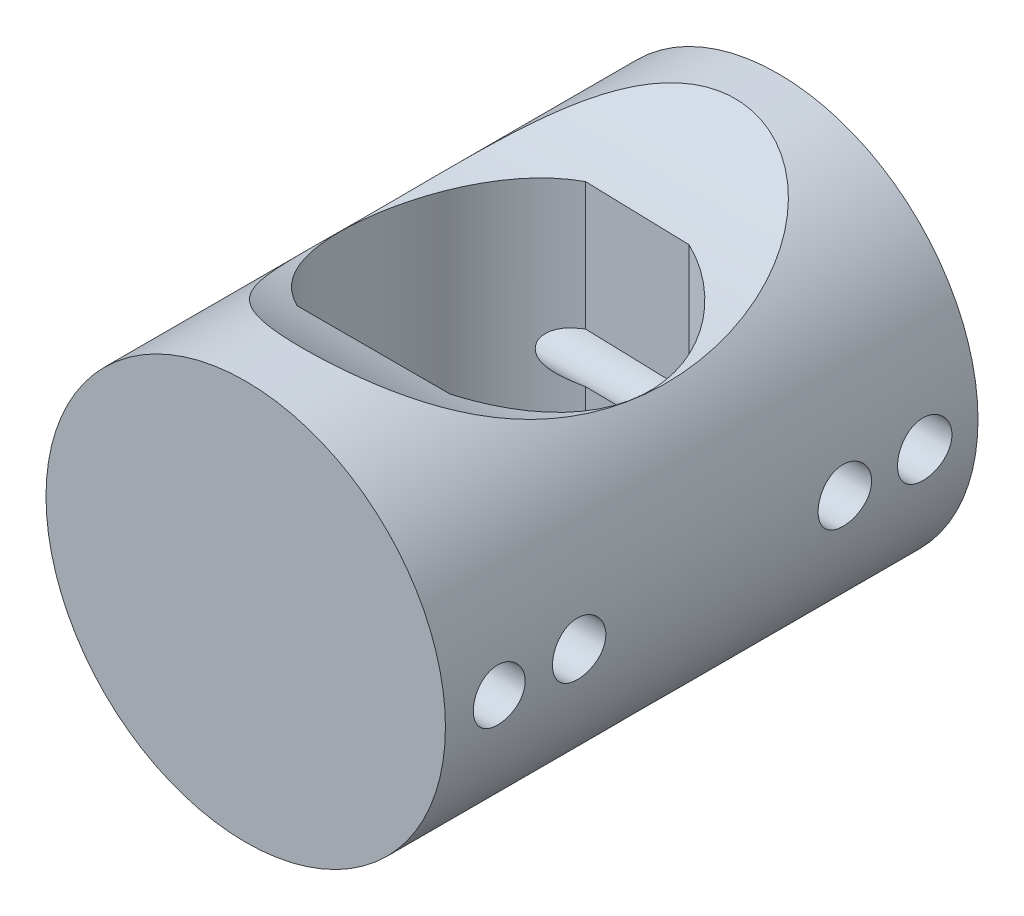
SolidWorks part; units mm, degrees
ref_plane "Front Plane" through (0, 0, 0) normal (0, 0, 1) x (1, 0, 0)
ref_plane "Top Plane" through (0, 0, 0) normal (0, 1, 0) x (1, 0, 0)
ref_plane "Right Plane" through (0, 0, 0) normal (1, 0, 0) x (0, 0, -1)
sketch "Sketch2" plane through (0, 0, 0) normal (0, 0, 1) x (1, 0, 0)
  circle A0 centre (0, 0) radius 19.05
extrude "Boss-Extrude1" add sketch "Sketch2" along normal blind 50.8
ref_plane "Plane1" through (-19.05, 0, 0) normal (-1, 0, 0) x (0, 0, 1)
sketch "Sketch3" plane through (-19.05, 0, 0) normal (-1, 0, 0) x (0, 0, 1)
  line L0 (0, 0) -> (50.7435, 0) construction
  circle A0 centre (5.08, 0) radius 2.5933
  circle A1 centre (12.7, 0) radius 2.5528
  circle A2 centre (45.6635, 0) radius 2.4772
  circle A3 centre (38.0435, 0) radius 2.546
  dimension "D1" = 12.7
  dimension "D2" = 12.7
  dimension "D3" = 5.08
  dimension "D4" = 5.08
extrude "Cut-Extrude1" cut sketch "Sketch3" against normal through all
sketch "Sketch4" plane through (-19.05, 0, 0) normal (-1, 0, 0) x (0, 0, 1)
  line L1 (50.8, 19.05) -> (0, 19.05) construction
  line L2 (45.3674, 19.05) -> (4.1123, 19.05)
  arc A1 (45.3674, 19.05) -> (4.1123, 19.05) centre (24.7399, 50.4085) cw
extrude "Cut-Extrude2" cut sketch "Sketch4" against normal through all
sketch "Sketch5" plane through (0, 0, 0) normal (0, 1, 0) x (1, 0, 0)
  line L0 (33.6509, -14.4282) -> (-32.2742, -13.039)
  line L1 (33.5941, -38.5977) -> (-34.3518, -38.5977)
  circle A0 centre (0, -26.7189) radius 13.9418
extrude "Cut-Extrude3" cut sketch "Sketch5" against normal through all both and the other way through all contours L1 A0 L0 region at (-0.0031, 0, 26.4215)
